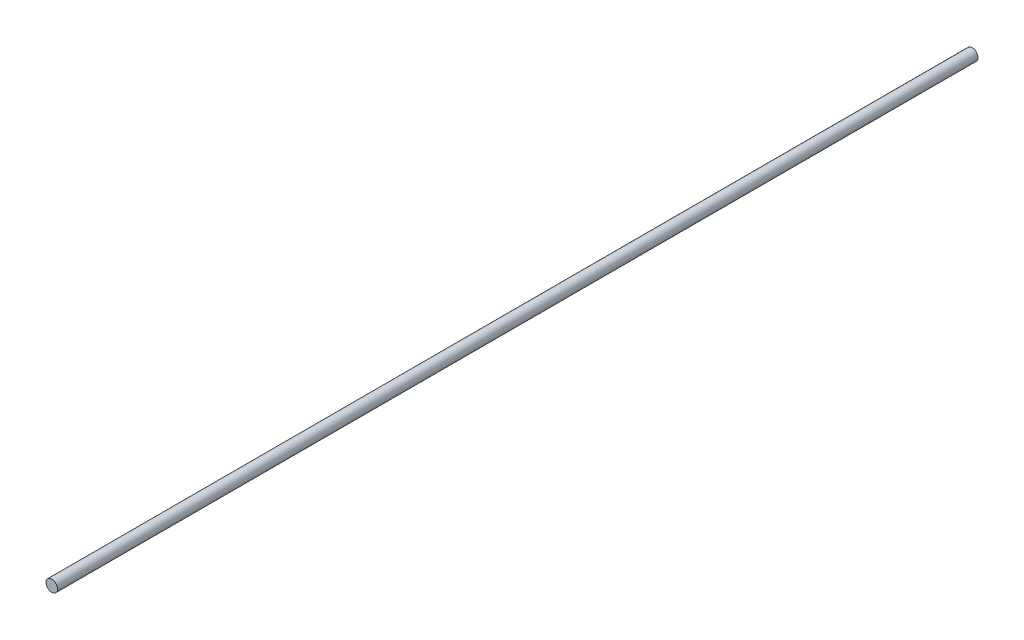
SolidWorks part; units mm, degrees
material "Plain Carbon Steel"
ref_plane "Front Plane" through (0, 0, 0) normal (0, 0, 1) x (1, 0, 0)
ref_plane "Top Plane" through (0, 0, 0) normal (0, 1, 0) x (1, 0, 0)
ref_plane "Right Plane" through (0, 0, 0) normal (1, 0, 0) x (0, 0, -1)
sketch "Sketch1" plane through (0, 0, 0) normal (0, 0, 1) x (1, 0, 0)
  circle A0 centre (0, 0) radius 2
  dimension "D1" = 4
extrude "Boss-Extrude1" add sketch "Sketch1" along normal blind 320
cosmetic thread "Cosmetic Thread1"
